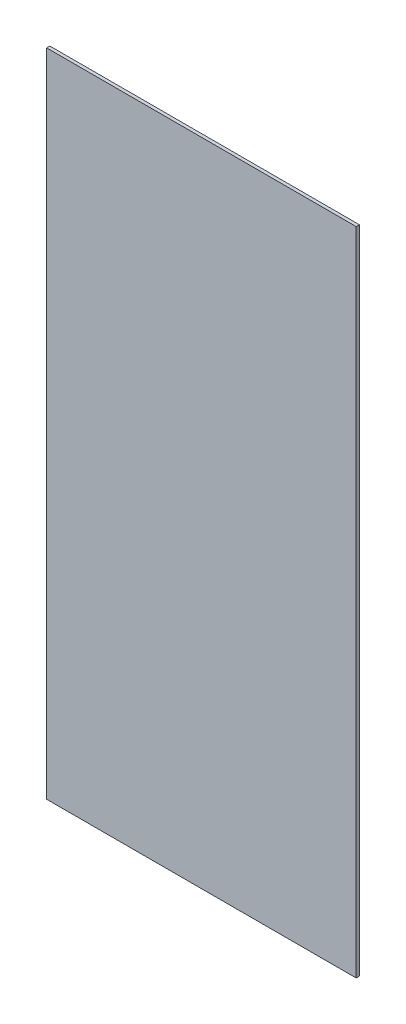
SolidWorks part; units mm, degrees
material "Acrylic (Medium-high impact)"
ref_plane "Front Plane" through (0, 0, 0) normal (0, 0, 1) x (1, 0, 0)
ref_plane "Top Plane" through (0, 0, 0) normal (0, 1, 0) x (1, 0, 0)
ref_plane "Right Plane" through (0, 0, 0) normal (1, 0, 0) x (0, 0, -1)
sketch "Sketch1" plane through (0, 0, 0) normal (0, 0, 1) x (1, 0, 0)
  line L1 (-145, 304.8) -> (145, 304.8)
  line L2 (-145, 304.8) -> (-145, -304.8)
  line L3 (-145, -304.8) -> (145, -304.8)
  line L4 (145, 304.8) -> (145, -304.8)
  line L5 (-145, 304.8) -> (145, -304.8) construction
  line L6 (-145, -304.8) -> (145, 304.8) construction
  point P0 (0, 0)
  dimension "D1" = 609.6
  dimension "D2" = 290
extrude "Boss-Extrude1" add sketch "Sketch1" along normal blind 3
